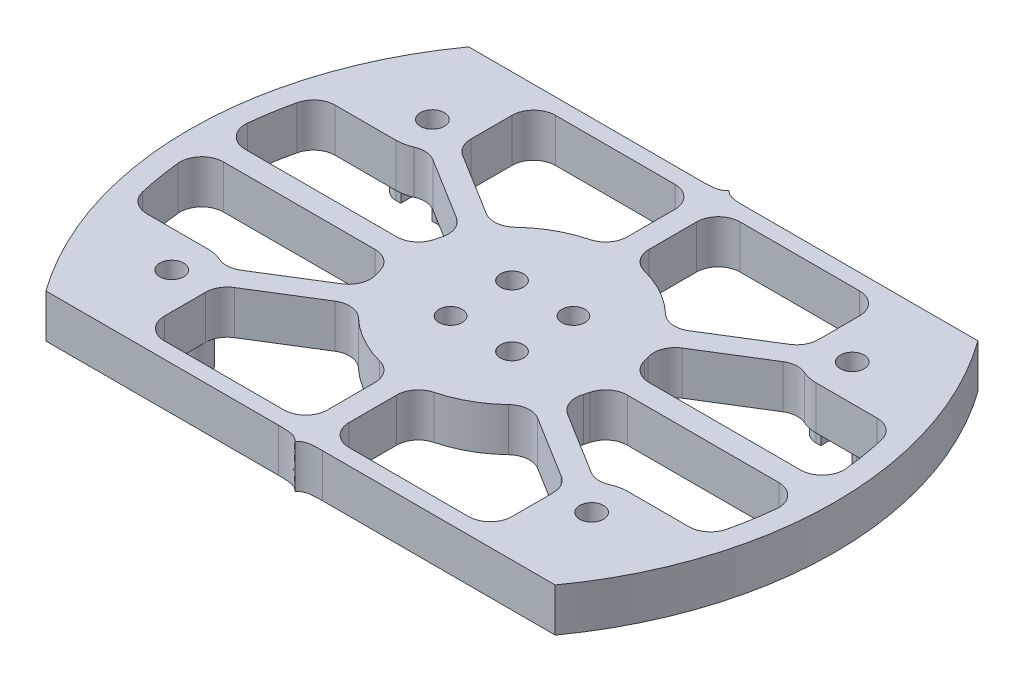
SolidWorks part; units mm, degrees
material "3.1355 (EN-AW 2024)"
ref_plane "Front" through (0, 0, 0) normal (0, 0, 1) x (1, 0, 0)
ref_plane "Top" through (0, 0, 0) normal (0, 1, 0) x (1, 0, 0)
ref_plane "Right" through (0, 0, 0) normal (1, 0, 0) x (0, 0, -1)
sketch "Эскиз1" plane through (0, 0, 0) normal (0, 1, 0) x (1, 0, 0)
  line L0 (0, 0) -> (0, 60) construction
  line L1 (0, 60) -> (10, 60) construction
  line L3 (79.1655, 0) -> (10, 0)
  line L4 (0, 30) -> (63.0426, 30) construction
  line L5 (10, 60) -> (79.1655, 60)
  line L6 (10, 0) -> (0, 0) construction
  line L7 (15.5828, 48) -> (73.5828, 48) construction
  line L8 (15.5828, 12) -> (73.5828, 12) construction
  line L9 (44.5828, 60) -> (44.5828, 0) construction
  arc A0 (10, 0) -> (10, 60) centre (50, 30) cw
  arc A1 (79.1655, 0) -> (79.1655, 60) centre (39.1655, 30) ccw
  point P5 (15.5828, 48)
  dimension "D3" = 50
  dimension "D1" = 60
  dimension "D2" = 12
  dimension "D4" = 38.84
  dimension "D5" = 58
extrude "Бобышка-Вытянуть1" add sketch "Эскиз1" along normal blind 6
sketch "Эскиз2" plane through (0, 6, 0) normal (0, 1, 0) x (1, 0, 0)
  line L4 (11.5292, 3) -> (77.6363, 3)
  line L5 (77.6363, 57) -> (11.5292, 57)
  line L6 (11.5292, 3) -> (77.6363, 3)
  line L7 (77.6363, 57) -> (11.5292, 57)
  arc A4 (11.5292, 57) -> (11.5292, 3) centre (50, 30) ccw
  arc A5 (77.6363, 3) -> (77.6363, 57) centre (39.1655, 30) ccw
  arc A6 (11.5292, 57) -> (11.5292, 3) centre (50, 30) ccw
  arc A7 (77.6363, 3) -> (77.6363, 57) centre (39.1655, 30) ccw
  dimension "D1" = 3
extrude "Вырез-Вытянуть1" cut sketch "Эскиз2" against normal through all
sketch "Эскиз3" plane through (0, 6, 0) normal (0, 1, 0) x (1, 0, 0)
  line L1 (89.1655, 30) -> (0, 30) construction
  circle A0 centre (15.5828, 48) radius 5
  circle A1 centre (73.5828, 48) radius 5
  arc A2 (79.1655, 0) -> (79.1655, 60) centre (39.1655, 30) ccw construction
  circle A3 centre (73.5828, 12) radius 5
  circle A4 centre (15.5828, 12) radius 5
  circle A5 centre (44.5828, 30) radius 15
  dimension "D1" = 10
  dimension "D2" = 10
  dimension "D3" = 30
extrude "Бобышка-Вытянуть2" add sketch "Эскиз3" against normal through all separate body
sketch "Эскиз4" plane through (0, 6, 0) normal (0, 1, 0) x (1, 0, 0)
  line L0 (77.6363, 57) -> (11.5292, 57) construction
  line L1 (11.5292, 3) -> (77.6363, 3) construction
  line L2 (77.6363, 57) -> (11.5292, 57) construction
  line L3 (11.5292, 3) -> (77.6363, 3) construction
  line L4 (44.5828, 45) -> (44.5828, 57) construction
  line L5 (31.8382, 37.9104) -> (19.831, 45.3632) construction
  line L6 (57.3274, 37.9104) -> (69.3346, 45.3632) construction
  line L7 (3, 30) -> (29.5828, 30) construction
  line L8 (86.1655, 30) -> (59.5828, 30) construction
  line L9 (57.3274, 22.0896) -> (69.3346, 14.6368) construction
  line L10 (31.8382, 22.0896) -> (19.831, 14.6368) construction
  line L11 (44.5828, 15) -> (44.5828, 3) construction
  line L12 (46.0828, 44.9248) -> (46.0828, 57)
  line L13 (32.6931, 39.1453) -> (20.4263, 46.7591)
  line L14 (58.0545, 36.5963) -> (70.3213, 44.2102)
  line L15 (56.4724, 20.8547) -> (68.7392, 13.2409)
  line L16 (43.0828, 15.0752) -> (43.0828, 3)
  line L17 (31.111, 23.4037) -> (18.8443, 15.7898)
  line L18 (43.0828, 44.9248) -> (43.0828, 57)
  line L19 (31.111, 36.5963) -> (18.8443, 44.2102)
  line L20 (56.4724, 39.1453) -> (68.7392, 46.7591)
  line L21 (58.0545, 23.4037) -> (70.3213, 15.7898)
  line L22 (46.0828, 15.0752) -> (46.0828, 3)
  line L23 (32.6931, 20.8547) -> (20.4263, 13.2409)
  line L24 (32.6292, 39.1849) -> (20.622, 46.6376) construction
  line L25 (31.0471, 36.636) -> (19.0399, 44.0887) construction
  line L26 (43.0828, 45) -> (43.0828, 57) construction
  line L27 (46.0828, 45) -> (46.0828, 57) construction
  line L28 (56.5363, 39.1849) -> (68.5435, 46.6376) construction
  line L29 (58.1184, 36.636) -> (70.1256, 44.0887) construction
  line L30 (58.1184, 23.364) -> (70.1256, 15.9113) construction
  line L31 (56.5363, 20.8151) -> (68.5435, 13.3624) construction
  line L32 (46.0828, 15) -> (46.0828, 3) construction
  line L33 (43.0828, 15) -> (43.0828, 3) construction
  line L34 (32.6292, 20.8151) -> (20.622, 13.3624) construction
  line L35 (31.0471, 23.364) -> (19.0399, 15.9113) construction
  line L36 (3.0239, 28.5) -> (29.658, 28.5)
  line L37 (86.1416, 31.5) -> (59.5076, 31.5)
  line L38 (3.0239, 31.5) -> (29.658, 31.5)
  line L39 (86.1416, 28.5) -> (59.5076, 28.5)
  line L40 (3, 31.5) -> (29.5828, 31.5) construction
  line L41 (3, 28.5) -> (29.5828, 28.5) construction
  line L42 (86.1655, 31.5) -> (59.5828, 31.5) construction
  line L43 (86.1655, 28.5) -> (59.5828, 28.5) construction
  line L44 (43.0828, 57) -> (46.0828, 57)
  line L45 (3.0239, 31.5) -> (2.4021, 31.5)
  line L46 (2.4021, 31.5) -> (2.4021, 28.5)
  line L47 (2.4021, 28.5) -> (3.0239, 28.5)
  line L48 (3.0239, 28.5) -> (2.938, 28.4918)
  line L49 (86.1416, 31.5) -> (86.6727, 31.5)
  line L50 (86.6727, 31.5) -> (86.6727, 28.5)
  line L51 (86.6727, 28.5) -> (86.1416, 28.5)
  line L52 (43.0828, 3) -> (46.0828, 3)
  arc A0 (11.5292, 57) -> (11.5292, 3) centre (50, 30) ccw construction
  circle A1 centre (44.5828, 30) radius 15
  arc A2 (43.0828, 15.0752) -> (46.0828, 15.0752) centre (44.5828, 30) ccw
  arc A3 (77.6363, 3) -> (77.6363, 57) centre (39.1655, 30) ccw construction
  arc A4 (11.5292, 57) -> (11.5292, 3) centre (50, 30) ccw construction
  arc A5 (77.6363, 3) -> (77.6363, 57) centre (39.1655, 30) ccw construction
  circle A6 centre (73.5828, 48) radius 5 construction
  circle A7 centre (73.5828, 12) radius 5 construction
  circle A8 centre (15.5828, 12) radius 5 construction
  circle A9 centre (15.5828, 48) radius 5 construction
  arc A10 (68.7392, 46.7591) -> (70.3213, 44.2102) centre (73.5828, 48) ccw
  arc A11 (70.3213, 15.7898) -> (68.7392, 13.2409) centre (73.5828, 12) ccw
  arc A12 (20.4263, 13.2409) -> (18.8443, 15.7898) centre (15.5828, 12) ccw
  arc A13 (18.8443, 44.2102) -> (20.4263, 46.7591) centre (15.5828, 48) ccw
  arc A14 (56.4724, 20.8547) -> (58.0545, 23.4037) centre (44.5828, 30) ccw
  arc A15 (31.111, 23.4037) -> (32.6931, 20.8547) centre (44.5828, 30) ccw
  arc A16 (59.5076, 28.5) -> (59.5076, 31.5) centre (44.5828, 30) ccw
  arc A17 (58.0545, 36.5963) -> (56.4724, 39.1453) centre (44.5828, 30) ccw
  arc A18 (29.658, 31.5) -> (29.658, 28.5) centre (44.5828, 30) ccw
  arc A19 (32.6931, 39.1453) -> (31.111, 36.5963) centre (44.5828, 30) ccw
  arc A20 (46.0828, 44.9248) -> (43.0828, 44.9248) centre (44.5828, 30) ccw
  circle M2 centre (44.5828, 30) radius 15
  dimension "D1" = 0
  dimension "D2" = 1.5
  dimension "D3" = 1.5
  dimension "D4" = 1.5
  dimension "D5" = 1.5
extrude "Бобышка-Вытянуть3" add sketch "Эскиз4" against normal through all contours A13 L19 L13 M2 | L44 L18 L12 M2 | A10 L20 L14 M2 | L51 L50 L49 L37 L39 M2 | A11 L21 L15 M2 | L16 L52 L22 M2 | A12 L23 L17 M2 | L46 L47 L36 L38 L45 M2 region at (44.5828, 6, -50.9875) region at (63.3528, 6, -41.6503) region at (25.8128, 6, -41.6503) region at (73.1152, 6, -30) region at (16.005, 6, -30) region at (63.3528, 6, -18.3497) region at (25.8128, 6, -18.3497) region at (44.5828, 6, -9.0125)
sketch "Эскиз5" plane through (0, 0, 0) normal (0, -1, 0) x (1, 0, 0)
  line L0 (20.5828, -3) -> (20.5828, -12)
  line L1 (11.5292, -3) -> (43.0828, -3) construction
  line L2 (44.5828, 0) -> (44.5828, -60) construction
  line L3 (0, -30) -> (89.1655, -30) construction
  line L4 (4.8336, -17) -> (15.5828, -17)
  line L5 (11.5292, -3) -> (20.5828, -3)
  line L6 (84.3319, -17) -> (73.5828, -17)
  line L7 (68.5828, -3) -> (68.5828, -12)
  line L8 (77.6363, -3) -> (68.5828, -3)
  line L9 (77.6363, -57) -> (68.5828, -57)
  line L10 (68.5828, -57) -> (68.5828, -48)
  line L11 (84.3319, -43) -> (73.5828, -43)
  line L12 (11.5292, -57) -> (20.5828, -57)
  line L13 (4.8336, -43) -> (15.5828, -43)
  line L14 (20.5828, -57) -> (20.5828, -48)
  arc A0 (79.1655, -60) -> (79.1655, 0) centre (39.1655, -30) ccw construction
  arc A1 (11.5292, -3) -> (3.0239, -28.5) centre (50, -30) ccw construction
  arc A3 (20.4263, -13.2409) -> (18.8443, -15.7898) centre (15.5828, -12) ccw construction
  arc A4 (11.5292, -3) -> (4.8336, -17) centre (50, -30) ccw
  arc A5 (20.5828, -12) -> (15.5828, -17) centre (15.5828, -12) ccw
  arc A6 (68.5828, -12) -> (73.5828, -17) centre (73.5828, -12) cw
  arc A7 (77.6363, -3) -> (84.3319, -17) centre (39.1655, -30) cw
  arc A8 (77.6363, -57) -> (84.3319, -43) centre (39.1655, -30) ccw
  arc A9 (68.5828, -48) -> (73.5828, -43) centre (73.5828, -48) ccw
  arc A10 (20.5828, -48) -> (15.5828, -43) centre (15.5828, -48) cw
  arc A11 (11.5292, -57) -> (4.8336, -43) centre (50, -30) cw
extrude "Бобышка-Вытянуть4" add sketch "Эскиз5" against normal through all
fillet "Скругление1" radius 3 40 edges at (70.3213, 3, -44.2102) (58.0545, 3, -36.5963) (59.5076, 3, -31.5) (59.5076, 3, -28.5) (58.0545, 3, -23.4037) (70.3213, 3, -15.7898) (84.3319, 3, -17) (86.1416, 3, -28.5) (86.1416, 3, -31.5) (84.3319, 3, -43) (56.4724, 3, -39.1453) (46.0828, 3, -44.9248) (46.0828, 3, -57) (68.5828, 3, -57) (68.7392, 3, -46.7591) (43.0828, 3, -44.9248) (43.0828, 3, -57) (20.5828, 3, -57) (32.6931, 3, -39.1453) (20.4263, 3, -46.7591) (31.111, 3, -36.5963) (18.8443, 3, -44.2102) (4.8336, 3, -43) (3.0239, 3, -31.5) (29.658, 3, -31.5) (29.658, 3, -28.5) (3.0239, 3, -28.5) (4.8336, 3, -17) (18.8443, 3, -15.7898) (31.111, 3, -23.4037) (43.0828, 3, -3) (20.5828, 3, -3) (20.4263, 3, -13.2409) (32.6931, 3, -20.8547) (43.0828, 3, -15.0752) (56.4724, 3, -20.8547) (46.0828, 3, -15.0752) (46.0828, 3, -3) (68.5828, 3, -3) (68.7392, 3, -13.2409)
sketch "Эскиз8" plane through (0, 0, 0) normal (0, -1, 0) x (1, 0, 0)
  line L0 (44.5828, 0) -> (44.5828, -60) construction
  line L1 (0, -30) -> (89.1655, -30) construction
  line L2 (9.4123, -0.8) -> (41.5278, -0.8)
  line L3 (79.1655, 0) -> (10, 0) construction
  line L4 (40.1307, -0.8) -> (42.9249, -0.8) construction
  line L5 (79.7532, -0.8) -> (47.6378, -0.8)
  line L6 (79.1655, 0) -> (10, 0)
  line L7 (79.1655, -60) -> (10, -60)
  line L8 (79.7532, -59.2) -> (47.6378, -59.2)
  line L9 (9.4123, -59.2) -> (41.5278, -59.2)
  arc A0 (79.1655, -60) -> (79.1655, 0) centre (39.1655, -30) ccw construction
  arc A1 (10, 0) -> (10, -60) centre (50, -30) ccw construction
  arc A2 (10, 0) -> (9.4123, -0.8) centre (50, -30) ccw
  arc A3 (79.7532, -0.8) -> (79.1655, 0) centre (39.1655, -30) ccw
  arc A4 (79.7532, -59.2) -> (79.1655, -60) centre (39.1655, -30) cw
  arc A5 (10, -60) -> (9.4123, -59.2) centre (50, -30) cw
  spline S0 degree 3 poles (44.5828, 0) (43.9591, -0.7036) (43.2742, -0.8) (41.5278, -0.8) knots 0 0 0 0 1 1 1 1
  spline S1 degree 3 poles (44.5828, 0) (45.2064, -0.7036) (45.8914, -0.8) (47.6378, -0.8) knots 0 0 0 0 1 1 1 1
  spline S2 degree 3 poles (44.5828, -60) (45.2064, -59.2964) (45.8914, -59.2) (47.6378, -59.2) knots 0 0 0 0 1 1 1 1
  spline S3 degree 3 poles (44.5828, -60) (43.9591, -59.2964) (43.2742, -59.2) (41.5278, -59.2) knots 0 0 0 0 1 1 1 1
  dimension "D1" = 0.8
extrude "Вырез-Вытянуть2" cut sketch "Эскиз8" against normal through all contours S0 L6 A2 L2 | L6 S1 L5 A3 | L7 S3 L9 A5 | S2 L7 A4 L8 region at (26.8398, 0, -0.3978) region at (62.3257, 0, -0.3978) region at (26.8398, 0, -59.6022) region at (62.3257, 0, -59.6022)
hole_wizard "Отверстие обработанное метчиком M4x0.71" positions "Эскиз7" profile "Эскиз6" tap size "M4x0.7" standard "Ansi Metric" end condition through all
sketch "Эскиз7" plane through (0, 0, 0) normal (0, -1, 0) x (-1, 0, 0)
  point P0 (-15.5828, 12)
  point P3 (-73.5828, 12)
  point P6 (-73.5828, 48)
  point P9 (-15.5828, 48)
sketch "Эскиз6" plane through (15.5828, 0, -12) normal (1, 0, 0) x (0, 0, -1)
  line L0 (0, 0) -> (0, 6)
  line L1 (0, 6) -> (1.65, 6)
  line L2 (1.65, 6) -> (1.65, 0)
  line L5 (1.65, 0) -> (0, 0)
  line L11 (0, -6.35) -> (0, 107.95) construction
  dimension "Диаметр проходного сверла" = 3.3
  dimension "Глубина проходного сверла" = 6
cosmetic thread "Отверстие резьбы1" parameters "D2"=4
cosmetic thread "Отверстие резьбы2" parameters "D2"=4
cosmetic thread "Отверстие резьбы3" parameters "D2"=4
cosmetic thread "Отверстие резьбы4" parameters "D2"=4
cosmetic thread "Отверстие резьбы6" parameters "D2"=4
cosmetic thread "Отверстие резьбы7" parameters "D2"=4
sketch "Эскиз9" plane through (0, 0, 0) normal (0, 1, 0) x (1, 0, 0)
  line L0 (15.5828, 50.2) -> (15.5828, 45.8) construction
  line L1 (12.7828, 50.2) -> (18.3828, 50.2)
  line L2 (12.7828, 45.8) -> (18.3828, 45.8)
  line L3 (20.5828, 54) -> (20.5828, 48.3308) construction
  line L4 (0, 30) -> (89.1655, 30) construction
  line L5 (44.5828, 60) -> (44.5828, 0) construction
  line L6 (12.7828, 14.2) -> (18.3828, 14.2)
  line L7 (12.7828, 9.8) -> (18.3828, 9.8)
  line L8 (76.3828, 45.8) -> (70.7828, 45.8)
  line L9 (76.3828, 50.2) -> (70.7828, 50.2)
  line L10 (76.3828, 9.8) -> (70.7828, 9.8)
  line L11 (76.3828, 14.2) -> (70.7828, 14.2)
  arc A1 (18.3828, 50.2) -> (18.3828, 45.8) centre (18.3828, 48) cw
  arc A3 (12.7828, 50.2) -> (12.7828, 45.8) centre (12.7828, 48) ccw
  arc A4 (9.4123, 59.2) -> (9.4123, 0.8) centre (50, 30) ccw construction
  arc A5 (79.7532, 0.8) -> (79.7532, 59.2) centre (39.1655, 30) ccw construction
  arc A6 (18.3828, 9.8) -> (18.3828, 14.2) centre (18.3828, 12) ccw
  arc A7 (12.7828, 9.8) -> (12.7828, 14.2) centre (12.7828, 12) cw
  arc A8 (76.3828, 50.2) -> (76.3828, 45.8) centre (76.3828, 48) cw
  arc A9 (70.7828, 50.2) -> (70.7828, 45.8) centre (70.7828, 48) ccw
  arc A10 (76.3828, 9.8) -> (76.3828, 14.2) centre (76.3828, 12) ccw
  arc A11 (70.7828, 9.8) -> (70.7828, 14.2) centre (70.7828, 12) cw
  point P2 (15.5828, 48)
  dimension "D2" = 2.2
  dimension "D1" = 4.4
extrude "Бобышка-Вытянуть5" add sketch "Эскиз9" against normal blind 4
hole_wizard "Отверстие обработанное метчиком M4x0.72" positions "Эскиз11" profile "Эскиз10" tap size "M4x0.7" standard "Ansi Metric" end condition through all
sketch "Эскиз11" plane through (0, -4, 0) normal (0, -1, 0) x (-1, 0, 0)
  point P0 (-73.5828, 48)
  point P3 (-15.5828, 48)
  point P6 (-15.5828, 12)
  point P9 (-73.5828, 12)
sketch "Эскиз10" plane through (73.5828, -4, -48) normal (1, 0, 0) x (0, 0, -1)
  line L0 (0, 0) -> (0, 10)
  line L1 (0, 10) -> (1.65, 10)
  line L2 (1.65, 10) -> (1.65, 0)
  line L5 (1.65, 0) -> (0, 0)
  line L11 (0, -6.35) -> (0, 107.95) construction
  dimension "Диаметр проходного сверла" = 3.3
  dimension "Глубина проходного сверла" = 10
cosmetic thread "Отверстие резьбы9" parameters "D2"=4
cosmetic thread "Отверстие резьбы10" parameters "D2"=4
sketch "Эскиз12" plane through (0, 0, 0) normal (0, -1, 0) x (1, 0, 0)
  circle A0 centre (44.5828, -30) radius 6 construction
  point P2 (44.5828, -24)
  point P7 (48.8254, -25.7574)
  point P8 (50.5828, -30)
  point P9 (48.8254, -34.2426)
  point P10 (44.5828, -36)
  point P11 (40.3401, -34.2426)
  point P12 (38.5828, -30)
  point P13 (40.3401, -25.7574)
  point P14 (44.5828, -30)
  dimension "D1" = 12
  dimension "D2" = 8
hole_wizard "Цековка для винта с внутренним шестигранником M31" positions "Эскиз14" profile "Эскиз13" counterbore size "M3" standard "Ansi Metric" end condition through all
sketch "Эскиз14" plane through (0, 0, 0) normal (0, -1, 0) x (-1, 0, 0)
  point P0 (-40.3401, 25.7574)
  point P3 (-48.8254, 25.7574)
  point P6 (-48.8254, 34.2426)
  point P9 (-40.3401, 34.2426)
sketch "Эскиз13" plane through (40.3401, 0, -25.7574) normal (1, 0, 0) x (0, 0, -1)
  line L0 (0, 0) -> (0, 6)
  line L1 (0, 6) -> (1.6, 6)
  line L3 (1.6, 6) -> (1.6, 3)
  line L4 (1.6, 3) -> (3.25, 3)
  line L5 (3.25, 3) -> (3.25, 0)
  line L7 (3.25, 0) -> (0, 0)
  line L11 (0, -6.35) -> (0, 107.95) construction
  dimension "Диаметр сквозного отверстия" = 3.2
  dimension "Глубина сквозного отверстия" = 6
  dimension "Диаметр цековки" = 6.5
  dimension "Глубина цековки" = 3
sketch "Эскиз15" plane through (0, -4, 0) normal (0, -1, 0) x (1, 0, 0)
  line L0 (13.4328, -9.8) -> (13.4328, -50.2)
  line L1 (12.7828, -9.8) -> (18.3828, -9.8) construction
  line L2 (18.3828, -50.2) -> (12.7828, -50.2) construction
  line L3 (15.5828, -10.35) -> (15.5828, -13.65) construction
  line L4 (17.7328, -9.8) -> (17.7328, -50.2)
  line L5 (13.4328, -9.8) -> (17.7328, -9.8)
  line L6 (13.4328, -50.2) -> (17.7328, -50.2)
  line L7 (44.5828, -30) -> (44.5828, -60) construction
  line L8 (75.7328, -50.2) -> (71.4328, -50.2)
  line L9 (75.7328, -9.8) -> (71.4328, -9.8)
  line L10 (71.4328, -9.8) -> (71.4328, -50.2)
  line L11 (75.7328, -9.8) -> (75.7328, -50.2)
  circle A0 centre (15.5828, -12) radius 1.65 construction
  point P6 (13.9328, -12)
  point P22 (75.2328, -12)
  dimension "D1" = 0.5
extrude "Вырез-Вытянуть3" cut sketch "Эскиз15" against normal up to surface (4 mm away) up to face at (40.3401, 0, -29.0074)
sketch "Эскиз16" plane through (0, 0, 0) normal (0, -1, 0) x (1, 0, 0)
  line L0 (0, -30) -> (0, -59.2) construction
  line L1 (9.4123, -59.2) -> (0, -59.2) construction
  arc A0 (9.4123, -0.8) -> (9.4123, -59.2) centre (50, -30) ccw construction
equation "\"D2@Эскиз3\"=\"D1@Эскиз3\""
